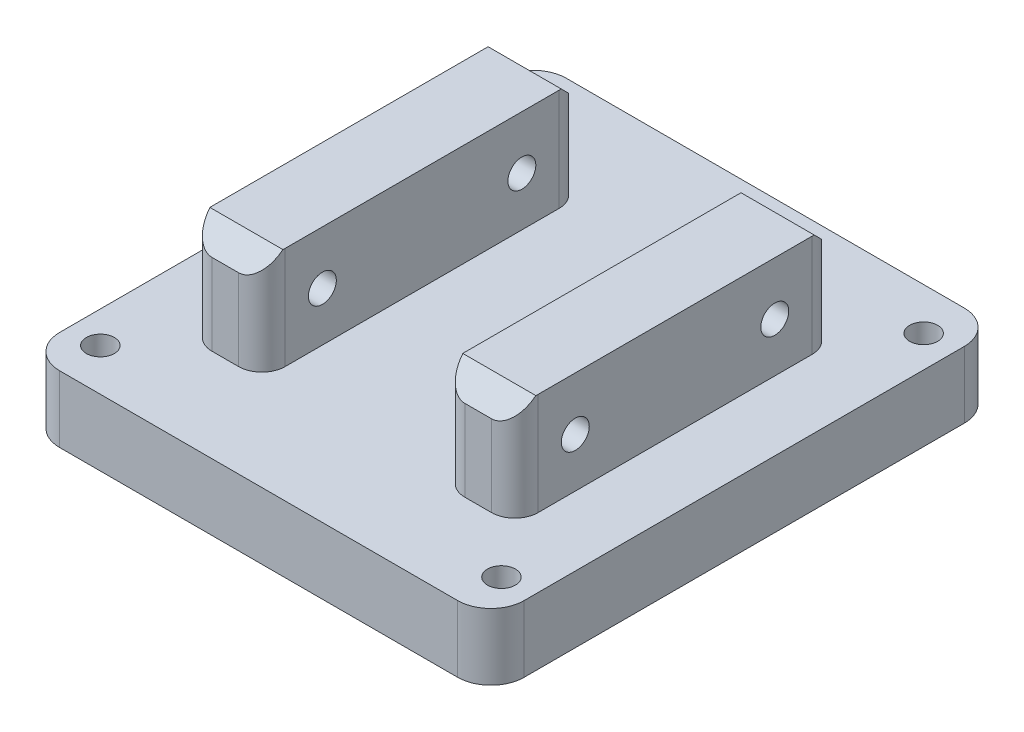
SolidWorks part; units mm, degrees
note: '?' marks a value the reader was unsure of.
material "Delrin 150"
ref_plane "Front Plane" through (0, 0, 0) normal (0, 0, 1) x (1, 0, 0)
ref_plane "Top Plane" through (0, 0, 0) normal (0, 1, 0) x (1, 0, 0)
ref_plane "Right Plane" through (0, 0, 0) normal (1, 0, 0) x (0, 0, -1)
ref_axis "Axis1" through (0, 0, -88.99) along (0, 0, 1)?
ref_axis "Axis2" through (0, 55, 0) along (0, -1, 0)?
ref_axis "Axis3" through (-88.99, 0, 0) along (1, 0, 0)?
sketch "Sketch1" plane through (0, 0, 0) normal (0, 0, 1) x (1, 0, 0)
  line L0 (-24.519, 25.4) -> (-24.519, 10)
  line L1 (-34.925, 0) -> (34.925, 0)
  line L2 (-24.519, 25.4) -> (-13.519, 25.4)
  line L3 (-13.519, 25.4) -> (-13.519, 10)
  line L4 (-13.519, 10) -> (13.519, 10)
  line L5 (-24.519, 10) -> (-34.925, 10)
  line L6 (-34.925, 10) -> (-34.925, 0)
  line L7 (34.925, 10) -> (34.925, 0)
  line L8 (0, 0) -> (0, 10) construction
  line L9 (24.519, 10) -> (34.925, 10)
  line L10 (13.519, 25.4) -> (13.519, 10)
  line L11 (24.519, 25.4) -> (13.519, 25.4)
  line L12 (24.519, 25.4) -> (24.519, 10)
  dimension "D1" = 11
  dimension "D2" = 25.4
  dimension "D3" = 49.038
  dimension "D4" = 69.85
  dimension "D5" = 10
extrude "Boss-Extrude1" add sketch "Sketch1" along normal mid plane 76.2
sketch "Sketch2" plane through (0, 25.4, 0) normal (0, 1, 0) x (1, 0, 0)
  line L1 (-24.519, 38.1) -> (24.519, 38.1)
  line L2 (-24.519, 38.1) -> (-24.519, 24.1)
  line L3 (-24.519, 24.1) -> (24.519, 24.1)
  line L4 (24.519, 38.1) -> (24.519, 24.1)
  line L5 (0, 0) -> (24.519, 0) construction
  line L6 (24.519, -38.1) -> (24.519, -24.1)
  line L7 (-24.519, -24.1) -> (24.519, -24.1)
  line L8 (-24.519, -38.1) -> (-24.519, -24.1)
  line L9 (-24.519, -38.1) -> (24.519, -38.1)
  line L10 (24.519, -38.1) -> (24.519, 38.1) construction
  dimension "D1" = 14
extrude "Cut-Extrude1" cut sketch "Sketch2" against normal up to surface (15.4 mm away) up to face at (0, 10, 0)
fillet "Fillet1" radius 3.5 8 edges at (-24.519, 17.7, -24.1) (-24.519, 17.7, 24.1) (24.519, 17.7, 24.1) (24.519, 17.7, -24.1) (13.519, 17.7, -24.1) (13.519, 17.7, 24.1) (-13.519, 17.7, -24.1) (-13.519, 17.7, 24.1)
hole_wizard "Tap Drill for M5x0.8 Tap2" positions "Sketch4" profile "Sketch3" hole size "M5x0.8" standard "ANSI Metric" end condition through all
sketch "Sketch4" plane through (0, 0, 0) normal (0, -1, 0) x (-1, 0, 0)
  line L0 (-34.925, 0) -> (0, 0) construction
  line L2 (0, 0) -> (0, 38.1) construction
  line L3 (34.925, 38.1) -> (-34.925, 38.1) construction
  line L8 (-34.925, -38.1) -> (-34.925, 38.1) construction
  point P0 (-30.1625, 31.75)
  point P14 (30.1625, 31.75)
  point P15 (30.1625, -31.75)
  point P16 (-30.1625, -31.75)
  dimension "D1" = 60.325
  dimension "D2" = 63.5
sketch "Sketch3" plane through (30.1625, 0, -31.75) normal (1, 0, 0) x (0, 0, -1)
  line L0 (0, 0) -> (0, 25.4)
  line L1 (0, 25.4) -> (2.1, 25.4)
  line L2 (2.1, 25.4) -> (2.1, 0)
  line L5 (2.1, 0) -> (0, 0)
  line L11 (0, -6.35) -> (0, 107.95) construction
  dimension "Thru Hole Dia." = 4.2
  dimension "Thru Hole Depth" = 25.4
hole_wizard "Tap Drill for M5x0.8 Tap3" positions "Sketch6" profile "Sketch5" hole size "M5x0.8" standard "ANSI Metric" end condition through all
sketch "Sketch6" plane through (-24.519, 0, 0) normal (-1, 0, 0) x (0, 0, 1)
  line L0 (0, 0) -> (0, 25.4) construction
  line L1 (38.1, 0) -> (-38.1, 0) construction
  line L2 (20.6, 25.4) -> (-20.6, 25.4) construction
  line L4 (-24.1, 17.4) -> (24.1, 17.4) construction
  line L5 (-24.1, 10) -> (-24.1, 25.4) construction
  line L6 (24.1, 25.4) -> (24.1, 10) construction
  point P2 (-15, 17.4)
  point P20 (15, 17.4)
  dimension "D1" = 30
  dimension "D2" = 8
sketch "Sketch5" plane through (-24.519, 17.4, -15) normal (0, 1, 0) x (0, 0, 1)
  line L0 (0, 0) -> (0, 59.444)
  line L1 (0, 59.444) -> (2.1, 59.444)
  line L2 (2.1, 59.444) -> (2.1, 0)
  line L5 (2.1, 0) -> (0, 0)
  line L11 (0, -6.35) -> (0, 107.95) construction
  dimension "Thru Hole Dia." = 4.2
  dimension "Thru Hole Depth" = 59.444
chamfer "Chamfer1" distance 3.175 angle 45 4 edges at (-19.019, 25.4, 24.1) (19.019, 25.4, 24.1) (-19.019, 25.4, -24.1) (19.019, 25.4, -24.1) tangent propagation no
fillet "Fillet2" [suppressed] radius 4.5
sketch "Sketch7" [suppressed] plane through (0, 25.4, 0) normal (0, 1, 0) x (1, 0, 0)
  line L0 (-24.519, -37.0759) -> (-24.519, 37.0759) construction
  line L1 (24.519, 37.75) -> (-24.519, 37.75)
  line L2 (24.519, 37.75) -> (24.519, 15.875)
  line L3 (24.519, 15.875) -> (-24.519, 15.875)
  line L4 (-24.519, 37.75) -> (-24.519, 15.875)
  line L5 (22.15, 37.75) -> (13.519, 37.75) construction
  line L6 (24.519, -37.0759) -> (24.519, 37.0759) construction
  line L7 (-13.519, -37.75) -> (-22.15, -37.75) construction
  line L8 (24.519, -31.125) -> (-24.519, -31.125)
  line L9 (24.519, -31.125) -> (24.519, -37.75)
  line L10 (24.519, -37.75) -> (-24.519, -37.75)
  line L11 (-24.519, -31.125) -> (-24.519, -37.75)
  line L12 (0, 0) -> (24.519, 0) construction
  dimension "D1" = 47
  dimension "D2" = 15.875
extrude "Cut-Extrude2" [suppressed] cut sketch "Sketch7" against normal up to surface (15.4 mm away)
fillet "Fillet3" [suppressed] radius 3.5
chamfer "Chamfer2" [suppressed] distance 4 angle 45
hole_wizard "CBORE for  SHCS1" [suppressed] positions "Sketch9" profile "Sketch8" counterbore size "M6" standard "ANSI Metric"
sketch "Sketch9" plane through (0, 10, 0) normal (0, 1, 0) x (1, 0, 0)
  line L0 (0, 0) -> (0, 37.75) construction
  line L1 (22.15, 37.75) -> (-22.15, 37.75) construction
  line L3 (0, 0) -> (26.65, 0) construction
  line L4 (26.65, -33.25) -> (26.65, 33.25) construction
  point P0 (13.5, 25.4)
  point P16 (9, -25.4)
  point P17 (-9, -25.4)
  point P18 (-13.5, 25.4)
  dimension "D1" = 25.4
  dimension "D2" = 27
  dimension "D3" = 18
  dimension "D4" = 25.4
sketch "Sketch8" plane through (13.5, 10, -25.4) normal (1, 0, 0) x (0, 0, 1)
  line L0 (0, 0) -> (0, 10)
  line L1 (0, 10) -> (2.75, 10)
  line L3 (2.75, 10) -> (2.75, 6)
  line L4 (2.75, 6) -> (5, 6)
  line L5 (5, 6) -> (5, 0)
  line L7 (5, 0) -> (0, 0)
  line L11 (0, -6.35) -> (0, 107.95) construction
  dimension "Thru Hole Dia." = 6.6
  dimension "Thru Hole Depth" = 10
  dimension "C'Bore Dia." = 11
  dimension "C'Bore Depth" = 6
hole_wizard "Tap Drill for M5x0.8 Tap1" [suppressed] positions "Sketch11" profile "Sketch10" hole size "M5x0.8" standard "ANSI Metric"
sketch "Sketch11" plane through (24.519, 0, 0) normal (1, 0, 0) x (0, 0, -1)
  line L0 (-31.125, 19.525) -> (15.875, 19.525) construction
  line L1 (-31.125, 10) -> (-31.125, 21.4) construction
  line L2 (15.875, 21.4) -> (15.875, 10) construction
  line L4 (-7.625, 19.525) -> (-7.625, 25.4) construction
  line L5 (-27.125, 25.4) -> (11.875, 25.4) construction
  line L6 (-27.625, 10) -> (12.375, 10) construction
  point P0 (7.375, 19.525)
  point P2 (-22.625, 19.525)
  dimension "D1" = 30
  dimension "D2" = 9.525
sketch "Sketch10" plane through (24.519, 19.525, -7.375) normal (0, 1, 0) x (0, 0, -1)
  line L0 (0, 0) -> (0, 51.169)
  line L1 (0, 51.169) -> (2.1, 51.169)
  line L2 (2.1, 51.169) -> (2.1, 0)
  line L5 (2.1, 0) -> (0, 0)
  line L11 (0, -6.35) -> (0, 107.95) construction
  dimension "Thru Hole Dia." = 4.2
  dimension "Thru Hole Depth" = 51.169
fillet "Fillet4" radius 5 4 edges at (34.925, 5, -38.1) (34.925, 5, 38.1) (-34.925, 5, 38.1) (-34.925, 5, -38.1)
sketch "Sketch12" [suppressed] plane through (0, 4, 0) normal (0, 1, 0) x (1, 0, 0)
  circle A0 centre (-9, -25.4) radius 5 construction
  circle A1 centre (9, -25.4) radius 5 construction
  circle A2 centre (-9, -25.4) radius 5
  circle A3 centre (9, -25.4) radius 5
extrude "Cut-Extrude3" [suppressed] cut sketch "Sketch12" along normal through all
